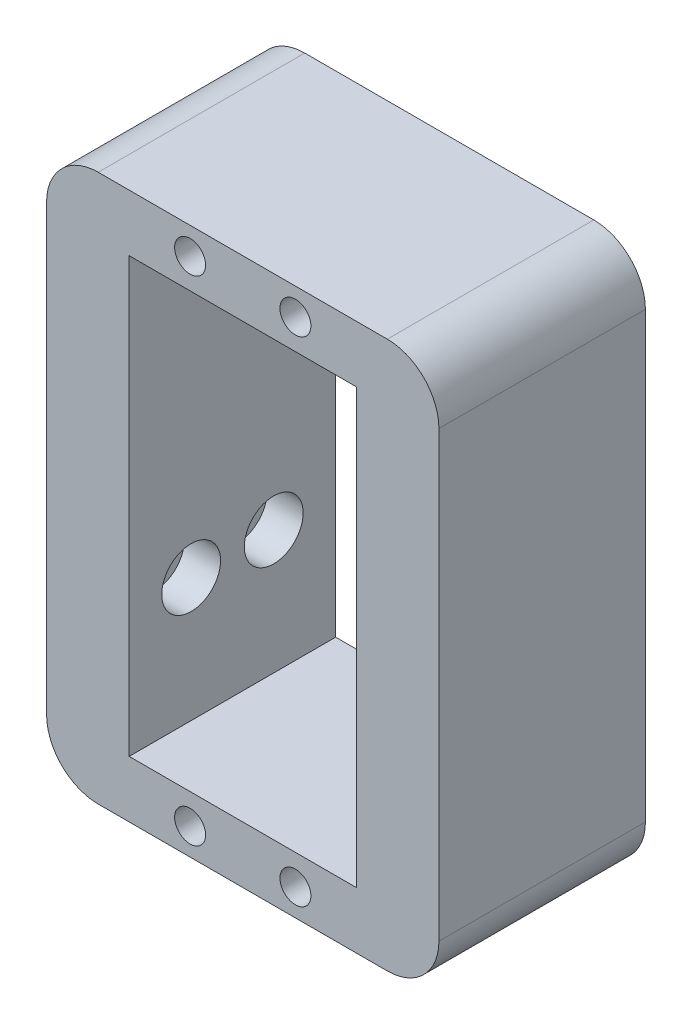
SolidWorks part; units mm, degrees
ref_plane "Front Plane" through (0, 0, 0) normal (0, 0, 1) x (1, 0, 0)
ref_plane "Top Plane" through (0, 0, 0) normal (0, 1, 0) x (1, 0, 0)
ref_plane "Right Plane" through (0, 0, 0) normal (1, 0, 0) x (0, 0, -1)
sketch "Sketch1" plane through (0, 0, 0) normal (0, 0, 1) x (1, 0, 0)
  line L1 (-11, 21) -> (11, 21)
  line L2 (-11, 21) -> (-11, -21)
  line L3 (-11, -21) -> (11, -21)
  line L4 (11, 21) -> (11, -21)
  line L5 (-11, 21) -> (11, -21) construction
  line L6 (-11, -21) -> (11, 21) construction
  line L8 (-19, 26.5) -> (19, 26.5)
  line L9 (-19, 26.5) -> (-19, -26.5)
  line L10 (-19, -26.5) -> (19, -26.5)
  line L11 (19, 26.5) -> (19, -26.5)
  line L12 (-19, 26.5) -> (19, -26.5) construction
  line L13 (-19, -26.5) -> (19, 26.5) construction
  point P0 (0, 0)
  point P6 (0, 0)
  dimension "D1" = 22
  dimension "D2" = 42
  dimension "D4" = 8
  dimension "D3" = 53
extrude "Boss-Extrude1" add sketch "Sketch1" along normal blind 20
sketch "Sketch4" plane through (0, 0, 0) normal (0, 0, -1) x (-1, 0, 0)
  circle A0 centre (-5.1, -23.9) radius 1.5
  circle A1 centre (5.1, -23.9) radius 1.5
  circle A2 centre (-5.1, 23.9) radius 1.5
  circle A3 centre (5.1, 23.9) radius 1.5
  dimension "D1" = 3
extrude "Cut-Extrude3" cut sketch "Sketch4" against normal through all
fillet "Fillet1" radius 5 4 edges at (-19, -26.5, 10) (19, -26.5, 10) (-19, 26.5, 10) (19, 26.5, 10)
sketch "Sketch5" plane through (-11, 0, 0) normal (1, 0, 0) x (0, 0, -1)
  line L0 (-20, 21) -> (-20, -21) construction
  line L1 (-20, -21) -> (0, -21) construction
  line L2 (0, 21) -> (0, -21) construction
  circle A0 centre (-14, -9) radius 2.85
  circle A1 centre (-14, -9) radius 1.75
  circle A2 centre (-6, -9) radius 2.85
  circle A3 centre (-6, -9) radius 1.75
  dimension "D1" = 5.7
  dimension "D2" = 3.5
  dimension "D3" = 6
  dimension "D4" = 12
  dimension "D6" = 6
  dimension "D5" = 2
extrude "Cut-Extrude4" cut sketch "Sketch5" against normal through all contours A1 | A3 region at (-11, -9, 14) region at (-11, -9, 6)
extrude "Cut-Extrude5" cut sketch "Sketch5<3>" against normal blind 3.5
sketch "Sketch5<3>" plane through (-11, 0, 0) normal (1, 0, 0) x (0, 0, -1) same geometry as "Sketch5"
